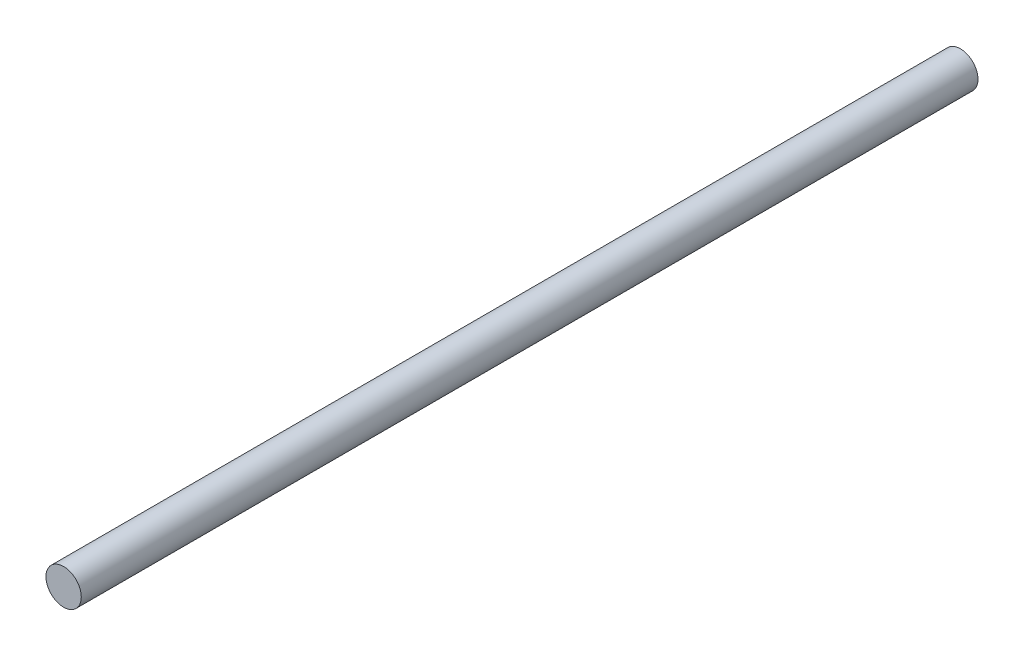
SolidWorks part; units mm, degrees
material "1060 Alloy"
ref_plane "Front Plane" through (0, 0, 0) normal (0, 0, 1) x (1, 0, 0)
ref_plane "Top Plane" through (0, 0, 0) normal (0, 1, 0) x (1, 0, 0)
ref_plane "Right Plane" through (0, 0, 0) normal (1, 0, 0) x (0, 0, -1)
sketch "Sketch2" plane through (0, 0, 0) normal (0, 0, 1) x (1, 0, 0)
  circle A0 centre (0, 0) radius 5
  dimension "D1" = 10
extrude "Boss-Extrude1" add sketch "Sketch2" along normal blind 254
